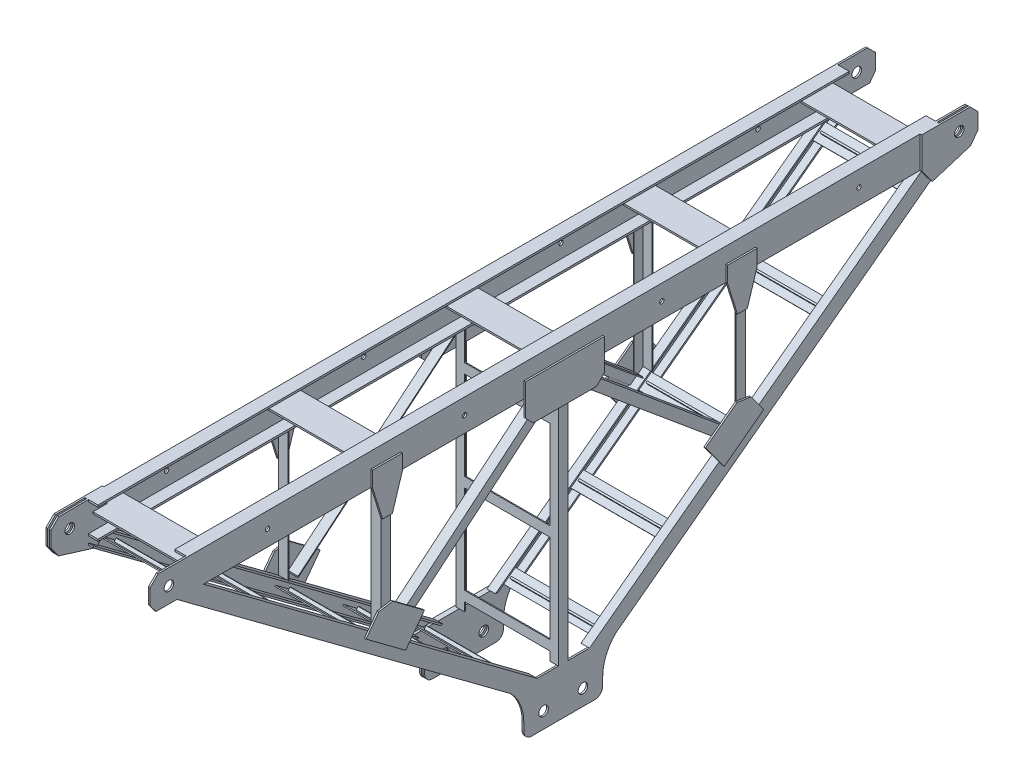
SolidWorks part; units mm, degrees
ref_plane "前视基准面" through (0, 0, 0) normal (0, 0, 1) x (1, 0, 0)
ref_plane "上视基准面" through (0, 0, 0) normal (0, 1, 0) x (1, 0, 0)
ref_plane "右视基准面" through (0, 0, 0) normal (1, 0, 0) x (0, 0, -1)
sketch "草图2" plane through (0, 0, 0) normal (0, 0, 1) x (1, 0, 0)
  line L0 (0, 0) -> (0, 160)
  line L1 (0, 160) -> (65, 160)
  line L2 (65, 160) -> (65, 150)
  line L3 (65, 150) -> (8.5, 150)
  line L4 (8.5, 150) -> (8.5, 10)
  line L5 (8.5, 10) -> (65, 10)
  line L6 (65, 10) -> (65, 0)
  line L7 (65, 0) -> (0, 0)
  line L8 (455, 160) -> (520, 160)
  line L9 (520, 160) -> (520, 0)
  line L10 (520, 0) -> (455, 0)
  line L11 (455, 0) -> (455, 10)
  line L12 (455, 10) -> (511.5, 10)
  line L13 (511.5, 10) -> (511.5, 150)
  line L14 (511.5, 150) -> (455, 150)
  line L15 (455, 150) -> (455, 160)
  dimension "D1" = 160
  dimension "D2" = 10
  dimension "D3" = 8.5
  dimension "D4" = 65
  dimension "D5" = 520
extrude "拉伸1" add sketch "草图2" along normal blind 4190
sketch "草图7" plane through (520, 0, 0) normal (1, 0, 0) x (0, 0, -1)
  line L1 (-2295, -1260) -> (-1895, -1260)
  line L2 (-2295, -1260) -> (-2295, -1500)
  line L3 (-2295, -1500) -> (-1895, -1500)
  line L4 (-1895, -1260) -> (-1895, -1500)
  line L5 (-4190, 160) -> (0, 160) construction
  line L6 (-2095, 160) -> (-2095, -1500) construction
  dimension "D1" = 240
  dimension "D2" = 400
  dimension "D4" = 1660
extrude "拉伸4" add sketch "草图7" against normal blind 520 separate body
sketch "草图8" plane through (0, -1260, 0) normal (0, 1, 0) x (1, 0, 0)
  line L0 (0, -2295) -> (520, -2295) construction
  line L1 (511.5, -2295) -> (8.5, -2295)
  line L2 (511.5, -2295) -> (511.5, -1895)
  line L3 (511.5, -1895) -> (8.5, -1895)
  line L4 (8.5, -2295) -> (8.5, -1895)
  line L5 (0, -1895) -> (520, -1895) construction
  line L6 (0, -1895) -> (0, -2295) construction
  line L7 (520, -1895) -> (520, -2295) construction
  dimension "D1" = 8.5
  dimension "D2" = 8.5
extrude "拉伸5" cut sketch "草图8" against normal through all
sketch "草图9" plane through (520, 0, 0) normal (1, 0, 0) x (0, 0, -1)
  line L0 (-2295, -1500) -> (-1895, -1500) construction
  circle A0 centre (-2195, -1420) radius 11
  circle A1 centre (-1995, -1420) radius 11
  point P6 (-2095, -1500)
  dimension "D1" = 22
  dimension "D2" = 80
  dimension "D3" = 80
  dimension "D4" = 200
  dimension "D5" = 100
extrude "拉伸6" cut sketch "草图9" against normal through all
sketch "草图13" plane through (520, 0, 0) normal (1, 0, 0) x (0, 0, -1)
  line L0 (-2295, -1260) -> (-4095, 80) construction
  line L1 (-95, 80) -> (-1895, -1260) construction
  line L2 (-1961.9855, -1260) -> (-1895, -1260)
  line L3 (-1895, -1260) -> (-2295, -1260) construction
  line L4 (-1895, -1260) -> (-1895, -1309.867)
  line L5 (-1895, -1500) -> (-1895, -1260) construction
  line L6 (-1895, -1309.867) -> (-135.4772, 0)
  line L7 (-4190, 0) -> (0, 0) construction
  line L8 (-135.4772, 0) -> (-269.4482, 0)
  line L9 (-269.4482, 0) -> (-1961.9855, -1260)
  line L10 (-2228.0145, -1260) -> (-2295, -1260)
  line L11 (-2295, -1260) -> (-2295, -1309.867)
  line L12 (-2295, -1260) -> (-2295, -1500) construction
  line L13 (-2295, -1309.867) -> (-4054.5228, 0)
  line L14 (-4054.5228, 0) -> (-3920.5518, 0)
  line L15 (-3920.5518, 0) -> (-2228.0145, -1260)
  line L16 (-4190, 160) -> (0, 160) construction
  line L17 (-4190, 0) -> (-4190, 160) construction
  line L18 (0, 0) -> (0, 160) construction
  dimension "D1" = 80
  dimension "D2" = 40
  dimension "D3" = 80
  dimension "D4" = 40
  dimension "D5" = 80
  dimension "D6" = 95
  dimension "D7" = 95
  dimension "D8" = 80
extrude "拉伸8" add sketch "草图13" against normal blind 43 separate body
sketch "草图14" plane through (477, 0, 0) normal (-1, 0, 0) x (0, 0, 1)
  line L0 (3933.9489, 0) -> (4041.1257, 0)
  line L1 (3920.5518, 0) -> (4054.5228, 0) construction
  line L2 (4041.1257, 0) -> (2295, -1299.8936)
  line L3 (2295, -1309.867) -> (2295, -1260) construction
  line L4 (2295, -1299.8936) -> (2295, -1260)
  line L5 (2295, -1260) -> (2241.4116, -1260)
  line L6 (2295, -1260) -> (2228.0145, -1260) construction
  line L7 (2241.4116, -1260) -> (3933.9489, 0)
  line L8 (4054.5228, 0) -> (2295, -1309.867) construction
  line L9 (2228.0145, -1260) -> (3920.5518, 0) construction
  line L10 (148.8743, 0) -> (256.0511, 0)
  line L11 (135.4772, 0) -> (269.4482, 0) construction
  line L12 (256.0511, 0) -> (1948.5884, -1260)
  line L13 (1961.9855, -1260) -> (1895, -1260) construction
  line L14 (1948.5884, -1260) -> (1895, -1260)
  line L15 (1895, -1260) -> (1895, -1299.8936)
  line L16 (1895, -1260) -> (1895, -1309.867) construction
  line L17 (1895, -1299.8936) -> (148.8743, 0)
  line L18 (1895, -1309.867) -> (135.4772, 0) construction
  line L19 (269.4482, 0) -> (1961.9855, -1260) construction
  dimension "D1" = 8
  dimension "D2" = 8
  dimension "D3" = 8
  dimension "D4" = 8
extrude "拉伸9" cut sketch "草图14" against normal blind 38
sketch "草图15" plane through (0, 0, 0) normal (-1, 0, 0) x (0, 0, 1)
  line L0 (4095, 80) -> (2295, -1260) construction
  line L1 (1895, -1500) -> (1895, -1260) construction
  line L2 (1895, -1260) -> (95, 80) construction
  line L3 (1895, -1260) -> (2295, -1260) construction
  line L4 (3920.5518, 0) -> (4054.5228, 0)
  line L5 (4190, 0) -> (0, 0) construction
  line L6 (4190, 0) -> (0, 0) construction
  line L7 (4054.5228, 0) -> (2295, -1309.867)
  line L8 (2295, -1260) -> (2295, -1500) construction
  line L9 (2295, -1309.867) -> (2295, -1260)
  line L10 (2295, -1260) -> (2228.0145, -1260)
  line L11 (2228.0145, -1260) -> (3920.5518, 0)
  line L12 (135.4772, 0) -> (269.4482, 0)
  line L13 (269.4482, 0) -> (1961.9855, -1260)
  line L14 (1961.9855, -1260) -> (1895, -1260)
  line L15 (1895, -1260) -> (1895, -1309.867)
  line L16 (1895, -1309.867) -> (135.4772, 0)
  line L17 (0, 0) -> (0, 160) construction
  line L18 (4190, 0) -> (4190, 160) construction
  line L19 (4190, 160) -> (0, 160) construction
  dimension "D1" = 40
  dimension "D2" = 40
  dimension "D3" = 80
  dimension "D4" = 40
  dimension "D5" = 80
  dimension "D6" = 95
  dimension "D7" = 95
  dimension "D8" = 80
extrude "拉伸10" add sketch "草图15" against normal blind 43 separate body
sketch "草图16" plane through (43, 0, 0) normal (1, 0, 0) x (0, 0, -1)
  line L0 (-3933.9489, 0) -> (-4041.1257, 0)
  line L1 (-4054.5228, 0) -> (-3920.5518, 0) construction
  line L2 (-4041.1257, 0) -> (-2295, -1299.8936)
  line L3 (-2295, -1260) -> (-2295, -1309.867) construction
  line L4 (-2295, -1299.8936) -> (-2295, -1260)
  line L5 (-2295, -1260) -> (-2241.4116, -1260)
  line L6 (-2228.0145, -1260) -> (-2295, -1260) construction
  line L7 (-2241.4116, -1260) -> (-3933.9489, 0)
  line L8 (-256.0511, 0) -> (-148.8743, 0)
  line L9 (-269.4482, 0) -> (-135.4772, 0) construction
  line L10 (-148.8743, 0) -> (-1895, -1299.8936)
  line L11 (-1895, -1309.867) -> (-1895, -1260) construction
  line L12 (-1895, -1299.8936) -> (-1895, -1260)
  line L13 (-1895, -1260) -> (-1948.5884, -1260)
  line L14 (-1895, -1260) -> (-1961.9855, -1260) construction
  line L15 (-1948.5884, -1260) -> (-256.0511, 0)
  line L16 (-135.4772, 0) -> (-1895, -1309.867) construction
  line L17 (-1961.9855, -1260) -> (-269.4482, 0) construction
  line L18 (-2295, -1309.867) -> (-4054.5228, 0) construction
  line L19 (-3920.5518, 0) -> (-2228.0145, -1260) construction
  dimension "D1" = 8
  dimension "D2" = 8
  dimension "D3" = 8
  dimension "D4" = 8
extrude "拉伸11" cut sketch "草图16" against normal blind 38
sketch "草图17" plane through (0, 0, 0) normal (-1, 0, 0) x (0, 0, 1)
  line L0 (4190, 160) -> (0, 160) construction
  line L1 (4190, 0) -> (0, 0) construction
  line L2 (2070, 0) -> (2120, 0)
  line L3 (2070, 0) -> (2070, -1260)
  line L4 (2070, -1260) -> (2120, -1260)
  line L5 (2120, 0) -> (2120, -1260)
  line L6 (1895, -1260) -> (2295, -1260) construction
  line L7 (2970, 0) -> (2970, -707.633)
  line L8 (3920.5518, 0) -> (2228.0145, -1260) construction
  line L9 (2970, -707.633) -> (3020, -670.4108)
  line L10 (3020, -670.4108) -> (3020, 0)
  line L11 (3020, 0) -> (2970, 0)
  line L12 (1170, 0) -> (1170, -670.4108)
  line L13 (4190, 160) -> (0, 160) construction
  line L14 (1170, -670.4108) -> (1220, -707.633)
  line L16 (1220, -707.633) -> (1220, 0)
  line L17 (1220, 0) -> (1170, 0)
  line L18 (1961.9855, -1260) -> (269.4482, 0) construction
  point P6 (2095, 160)
  point P22 (2095, 160)
  point P26 (2095, 160)
  dimension "D2" = 875
  dimension "D4" = 875
  dimension "D1" = 50
  dimension "D3" = 50
  dimension "D5" = 50
  dimension "D6" = 25
extrude "拉伸12" add sketch "草图17" against normal blind 520 separate body
sketch "草图18" plane through (0, -1260, 0) normal (0, -1, 0) x (1, 0, 0)
  line L0 (5, 2115) -> (43, 2115)
  line L1 (43, 2115) -> (43, 2120)
  line L2 (520, 2120) -> (0, 2120) construction
  line L3 (43, 2120) -> (477, 2120)
  line L4 (477, 2120) -> (477, 2115)
  line L5 (477, 2115) -> (515, 2115)
  line L6 (515, 2115) -> (515, 2070)
  line L9 (520, 2070) -> (0, 2070) construction
  line L10 (515, 2070) -> (5, 2070)
  line L14 (5, 2070) -> (5, 2115)
  line L15 (0, 2295) -> (0, 1895) construction
  line L16 (520, 2295) -> (520, 1895) construction
  dimension "D1" = 5
  dimension "D2" = 5
  dimension "D3" = 5
  dimension "D4" = 43
extrude "拉伸13" cut sketch "草图18" against normal blind 1260
sketch "草图22" plane through (0, 0, 3020) normal (0, 0, 1) x (1, 0, 0)
  line L0 (520, 0) -> (0, 0) construction
  line L1 (65, 0) -> (455, 0)
  line L2 (65, 0) -> (65, -1000)
  line L3 (65, -1000) -> (455, -1000)
  line L4 (455, 0) -> (455, -1000)
  line L6 (520, 0) -> (520, -1309.867) construction
  line L7 (0, -1309.867) -> (0, 0) construction
  dimension "D1" = 65
  dimension "D2" = 65
  dimension "D3" = 1000
extrude "拉伸14" cut sketch "草图22" against normal through all
sketch "草图23" plane through (455, 0, 0) normal (-1, 0, 0) x (0, 0, 1)
  line L1 (1170, 0) -> (1220, 0)
  line L2 (1170, 0) -> (1170, -707.633)
  line L3 (1170, -707.633) -> (1220, -707.633)
  line L4 (1220, 0) -> (1220, -707.633)
  line L5 (3020, 0) -> (2970, 0)
  line L6 (3020, 0) -> (3020, -707.633)
  line L7 (3020, -707.633) -> (2970, -707.633)
  line L8 (2970, 0) -> (2970, -707.633)
extrude "拉伸15" cut sketch "草图23" against normal blind 15
sketch "草图25" plane through (65, 0, 0) normal (1, 0, 0) x (0, 0, -1)
  line L1 (-2970, -707.633) -> (-3020, -707.633)
  line L2 (-2970, -707.633) -> (-2970, 0)
  line L3 (-2970, 0) -> (-3020, 0)
  line L4 (-3020, -707.633) -> (-3020, 0)
  line L5 (-1220, -707.633) -> (-1170, -707.633)
  line L6 (-1220, -707.633) -> (-1220, 0)
  line L7 (-1220, 0) -> (-1170, 0)
  line L8 (-1170, -707.633) -> (-1170, 0)
extrude "拉伸16" cut sketch "草图25" against normal blind 15
sketch "草图26" plane through (50, 0, 0) normal (1, 0, 0) x (0, 0, -1)
  line L0 (-3015, 0) -> (-2970, 0)
  line L1 (-2970, 0) -> (-3020, 0) construction
  line L2 (-2970, 0) -> (-2970, -707.633)
  line L3 (-2970, -707.633) -> (-3015, -674.133)
  line L4 (-2970, -707.633) -> (-3020, -670.4108) construction
  line L5 (-3015, -674.133) -> (-3015, 0)
  line L6 (-1175, 0) -> (-1220, 0)
  line L7 (-1170, 0) -> (-1220, 0) construction
  line L8 (-1220, 0) -> (-1220, -707.633)
  line L9 (-1220, -707.633) -> (-1175, -674.133)
  line L10 (-1220, -707.633) -> (-1170, -670.4108) construction
  line L11 (-1175, -674.133) -> (-1175, 0)
  line L12 (-1170, -670.4108) -> (-1170, 0) construction
  line L13 (-3020, 0) -> (-3020, -670.4108) construction
  dimension "D1" = 5
  dimension "D2" = 5
extrude "拉伸17" cut sketch "草图26" against normal blind 45
sketch "草图27" plane through (470, 0, 0) normal (-1, 0, 0) x (0, 0, 1)
  line L0 (3015, 0) -> (2970, 0)
  line L1 (3020, 0) -> (2970, 0) construction
  line L2 (2970, 0) -> (2970, -707.633)
  line L3 (2970, -707.633) -> (3015, -674.133)
  line L4 (2970, -707.633) -> (3020, -670.4108) construction
  line L5 (3015, -674.133) -> (3015, 0)
  line L6 (1175, 0) -> (1220, 0)
  line L7 (1220, 0) -> (1170, 0) construction
  line L8 (1220, 0) -> (1220, -707.633)
  line L9 (1220, -707.633) -> (1175, -674.133)
  line L10 (1220, -707.633) -> (1170, -670.4108) construction
  line L11 (1175, -674.133) -> (1175, 0)
  line L12 (3020, -670.4108) -> (3020, 0) construction
  line L13 (1170, 0) -> (1170, -670.4108) construction
  dimension "D1" = 5
  dimension "D2" = 5
extrude "拉伸18" cut sketch "草图27" against normal blind 45
sketch "草图28" plane through (0, 0, 0) normal (-1, 0, 0) x (0, 0, 1)
  line L0 (2070, 0) -> (1220, -707.633) construction
  line L1 (2970, -707.633) -> (2120, 0) construction
  line L2 (2120, -32.5295) -> (2120, 0)
  line L3 (2120, -1260) -> (2120, 0) construction
  line L4 (2120, 0) -> (2159.0741, 0)
  line L5 (4190, 0) -> (0, 0) construction
  line L6 (2159.0741, 0) -> (2970, -675.1035)
  line L7 (2970, 0) -> (2970, -707.633) construction
  line L8 (2970, -675.1035) -> (2970, -707.633)
  line L9 (2970, -707.633) -> (2949.3719, -722.9895)
  line L10 (3920.5518, 0) -> (2228.0145, -1260) construction
  line L11 (2949.3719, -722.9895) -> (2120, -32.5295)
  line L12 (2030.9259, 0) -> (2070, 0)
  line L13 (2070, 0) -> (2070, -32.5295)
  line L14 (2070, 0) -> (2070, -1260) construction
  line L15 (2070, -32.5295) -> (1240.6281, -722.9895)
  line L16 (1961.9855, -1260) -> (269.4482, 0) construction
  line L17 (1240.6281, -722.9895) -> (1220, -707.633)
  line L18 (1220, -707.633) -> (1220, -675.1035)
  line L19 (1220, -707.633) -> (1220, 0) construction
  line L20 (1220, -675.1035) -> (2030.9259, 0)
  dimension "D1" = 25
  dimension "D2" = 50
  dimension "D3" = 25
  dimension "D4" = 50
extrude "拉伸19" add sketch "草图28" against normal blind 50
sketch "草图29" plane through (50, 0, 0) normal (1, 0, 0) x (0, 0, -1)
  line L0 (-2038.7408, 0) -> (-2070, 0)
  line L1 (-2070, 0) -> (-2030.9259, 0) construction
  line L2 (-2070, 0) -> (-2070, -32.5295)
  line L3 (-2070, -32.5295) -> (-1240.6281, -722.9895)
  line L4 (-1240.6281, -722.9895) -> (-1220, -707.633)
  line L5 (-1220, -707.633) -> (-1220, -681.6094)
  line L6 (-1220, -675.1035) -> (-1220, -707.633) construction
  line L7 (-1220, -681.6094) -> (-2038.7408, 0)
  line L8 (-2030.9259, 0) -> (-1220, -675.1035) construction
  line L9 (-2151.2592, 0) -> (-2120, 0)
  line L10 (-2159.0741, 0) -> (-2120, 0) construction
  line L11 (-2120, 0) -> (-2120, -32.5295)
  line L12 (-2120, -32.5295) -> (-2949.3719, -722.9895)
  line L13 (-2949.3719, -722.9895) -> (-2970, -707.633)
  line L14 (-2970, -707.633) -> (-2970, -681.6094)
  line L15 (-2970, -707.633) -> (-2970, -675.1035) construction
  line L16 (-2970, -681.6094) -> (-2151.2592, 0)
  line L17 (-2970, -675.1035) -> (-2159.0741, 0) construction
  dimension "D1" = 5
  dimension "D2" = 5
extrude "拉伸20" cut sketch "草图29" against normal blind 45
sketch "草图30" plane through (520, 0, 0) normal (1, 0, 0) x (0, 0, -1)
  line L0 (-2070, 0) -> (-1220, -707.633) construction
  line L1 (-1240.6281, -722.9895) -> (-1175, -674.133) construction
  line L2 (-1220, -707.633) -> (-1220, 0) construction
  line L3 (-2120, 0) -> (-2970, -707.633) construction
  line L4 (-2070, 0) -> (-2030.9259, 0)
  line L5 (-4190, 0) -> (0, 0) construction
  line L6 (-2030.9259, 0) -> (-1220, -675.1035)
  line L7 (-1220, -675.1035) -> (-1220, -707.633)
  line L8 (-1220, -707.633) -> (-1240.6281, -722.9895)
  line L9 (-269.4482, 0) -> (-1961.9855, -1260) construction
  line L10 (-1240.6281, -722.9895) -> (-2070, -32.5295)
  line L11 (-2070, 0) -> (-2070, -1260) construction
  line L12 (-2070, -32.5295) -> (-2070, 0)
  line L13 (-2120, 0) -> (-2120, -32.5295)
  line L14 (-2120, -1260) -> (-2120, 0) construction
  line L15 (-2120, -32.5295) -> (-2949.3719, -722.9895)
  line L16 (-2228.0145, -1260) -> (-3920.5518, 0) construction
  line L17 (-2949.3719, -722.9895) -> (-2970, -707.633)
  line L18 (-2970, -707.633) -> (-2970, -675.1035)
  line L19 (-2970, 0) -> (-2970, -707.633) construction
  line L20 (-2970, -675.1035) -> (-2159.0741, 0)
  line L21 (-2159.0741, 0) -> (-2120, 0)
  dimension "D1" = 50
  dimension "D2" = 25
  dimension "D3" = 25
  dimension "D4" = 50
extrude "拉伸21" add sketch "草图30" against normal blind 50
sketch "草图31" plane through (470, 0, 0) normal (-1, 0, 0) x (0, 0, 1)
  line L0 (2120, 0) -> (2151.2592, 0)
  line L1 (2120, 0) -> (2159.0741, 0) construction
  line L2 (2151.2592, 0) -> (2970, -681.6094)
  line L3 (2970, -675.1035) -> (2970, -707.633) construction
  line L4 (2970, -681.6094) -> (2970, -707.633)
  line L5 (2970, -707.633) -> (2949.3719, -722.9895)
  line L6 (2949.3719, -722.9895) -> (2120, -32.5295)
  line L7 (2120, -32.5295) -> (2120, 0)
  line L8 (2038.7408, 0) -> (2070, 0)
  line L9 (2030.9259, 0) -> (2070, 0) construction
  line L10 (2070, 0) -> (2070, -32.5295)
  line L11 (2070, -32.5295) -> (1240.6281, -722.9895)
  line L12 (1240.6281, -722.9895) -> (1220, -707.633)
  line L13 (1220, -707.633) -> (1220, -681.6094)
  line L14 (1220, -707.633) -> (1220, -675.1035) construction
  line L15 (1220, -681.6094) -> (2038.7408, 0)
  line L16 (1220, -675.1035) -> (2030.9259, 0) construction
  line L17 (2159.0741, 0) -> (2970, -675.1035) construction
  dimension "D1" = 5
  dimension "D2" = 5
extrude "拉伸22" cut sketch "草图31" against normal blind 45
sketch "草图32" plane through (0, 0, 0) normal (-1, 0, 0) x (0, 0, 1)
  line L0 (0, 80) -> (4190, 80) construction
  line L1 (1120, 80) -> (1270, 80)
  line L2 (1895, 80) -> (2295, 80)
  line L3 (1895, 80) -> (1895, -120)
  line L4 (1895, -120) -> (2295, -120)
  line L5 (2295, 80) -> (2295, -120)
  line L6 (1270, 80) -> (1270, 0)
  line L7 (2030.9259, 0) -> (1220, 0) construction
  line L8 (1270, 0) -> (1220, -160)
  line L9 (1220, -675.1035) -> (1220, 0) construction
  line L10 (1220, -160) -> (1170, -160)
  line L11 (1170, 0) -> (1170, -670.4108) construction
  line L12 (1170, -160) -> (1120, 0)
  line L13 (1170, 0) -> (269.4482, 0) construction
  line L14 (1120, 0) -> (1120, 80)
  line L15 (2920, 80) -> (3070, 80)
  line L16 (3070, 80) -> (3070, 0)
  line L17 (3920.5518, 0) -> (3020, 0) construction
  line L18 (3070, 0) -> (3020, -160)
  line L19 (3020, -670.4108) -> (3020, 0) construction
  line L20 (3020, -160) -> (2970, -160)
  line L21 (2970, 0) -> (2970, -675.1035) construction
  line L22 (2970, -160) -> (2920, 0)
  line L23 (2970, 0) -> (2159.0741, 0) construction
  line L24 (2920, 0) -> (2920, 80)
  line L25 (2807.6858, -666.3992) -> (3008.2193, -517.1132)
  line L26 (2807.6858, -666.3992) -> (2903.2289, -794.7406)
  line L27 (3008.2193, -517.1132) -> (3103.7624, -645.4546)
  line L28 (2903.2289, -794.7406) -> (3103.7624, -645.4546)
  line L29 (2295, -1309.867) -> (4054.5228, 0) construction
  line L30 (2970, -675.1035) -> (3033.3528, -760.2043) construction
  line L31 (1181.7807, -517.1132) -> (1382.3142, -666.3992)
  line L32 (1181.7807, -517.1132) -> (1086.2376, -645.4546)
  line L33 (1382.3142, -666.3992) -> (1286.7711, -794.7406)
  line L34 (1086.2376, -645.4546) -> (1286.7711, -794.7406)
  line L35 (4190, 160) -> (0, 160) construction
  line L36 (0, 0) -> (0, 160) construction
  line L37 (4190, 0) -> (4190, 160) construction
  line L38 (135.4772, 0) -> (1895, -1309.867) construction
  line L39 (1220, -675.1035) -> (1156.6472, -760.2043) construction
  point P8 (2095, 160)
  dimension "D3" = 200
  dimension "D1" = 400
  dimension "D2" = 200
  dimension "D4" = 150
  dimension "D5" = 240
  dimension "D6" = 150
  dimension "D7" = 240
  dimension "D8" = 250
  dimension "D9" = 160
  dimension "D10" = 50
  dimension "D11" = 125
  dimension "D12" = 250
  dimension "D13" = 160
  dimension "D14" = 50
  dimension "D15" = 125
extrude "拉伸23" add sketch "草图32" along normal blind 8.5
pattern_linear "阵列(线性)7" count 2 spacing 528.5 along (1, 0, 0) of "拉伸23"
sketch "草图33" plane through (0, 0, 0) normal (-1, 0, 0) x (0, 0, 1)
  line L0 (217.5, 86.5) -> (293.25, 86.5)
  line L1 (217.5, 95) -> (377.5, 95)
  line L2 (217.5, 95) -> (217.5, 86.5)
  line L3 (301.75, 86.5) -> (377.5, 86.5)
  line L4 (377.5, 95) -> (377.5, 86.5)
  line L5 (95, 80) -> (4190, 80) construction
  line L6 (293.25, 86.5) -> (293.25, 46.5)
  line L7 (293.25, 46.5) -> (301.75, 46.5)
  line L8 (301.75, 86.5) -> (301.75, 46.5)
  line L9 (0, 160) -> (0, 0) construction
  line L11 (4190, 0) -> (4190, 160) construction
  dimension "D1" = 160
  dimension "D2" = 8.5
  dimension "D3" = 40
  dimension "D4" = 15
  dimension "D5" = 122.5
  dimension "D6" = 95
extrude "拉伸24" add sketch "草图33" against normal blind 520
pattern_linear "阵列(线性)8" count 5 spacing 900 along (0, 0, 1) of "拉伸24"
sketch "草图34" plane through (0, 0, 0) normal (-1, 0, 0) x (0, 0, 1)
  line L0 (3033.3528, -760.2043) -> (2970, -675.1035) construction
  line L1 (2295, -1309.867) -> (4054.5228, 0) construction
  line L2 (2975.8889, -749.9994) -> (2978.8746, -754.0101)
  line L3 (2975.8889, -749.9994) -> (3040.0596, -702.2279)
  line L4 (2978.8746, -754.0101) -> (3043.0453, -706.2385)
  line L5 (3040.0596, -702.2279) -> (3043.0453, -706.2385)
  dimension "D1" = 5
  dimension "D2" = 80
  dimension "D3" = 40
  dimension "D4" = 37.5
extrude "拉伸25" add sketch "草图34" against normal blind 512
sketch "草图35" plane through (0, -1907.9835, 1420.3877) normal (0, 0.8021, -0.5971) x (1, 0, 0)
  line L1 (40, -1973.2037) -> (480, -1973.2037)
  line L2 (40, -1973.2037) -> (40, -1981.7037)
  line L3 (40, -1981.7037) -> (480, -1981.7037)
  line L4 (480, -1973.2037) -> (480, -1981.7037)
  line L7 (0, -2056.5567) -> (0, -1954.1491) construction
  line L8 (520, -2056.5567) -> (520, -1954.1491) construction
  line L9 (512, -2019.2037) -> (5, -2019.2037) construction
  dimension "D1" = 40
  dimension "D2" = 40
  dimension "D3" = 8.5
  dimension "D4" = 37.5
extrude "拉伸26" add sketch "草图35" along normal blind 15
pattern_linear "阵列(线性)9" count 3 spacing 430 along (0, -0.5971, -0.8021) of "拉伸25", "拉伸26"
pattern_linear "阵列(线性)10" count 3 spacing 550 along (0, 0.5971, 0.8021) of "拉伸25", "拉伸26"
ref_plane "基准面2" through (0, 0, 2095) normal (0, 0, 1) x (1, 0, 0)
mirror "镜向13" about plane through (0, 0, 2095) normal (0, 0, 1) of "阵列(线性)10", "阵列(线性)9", "拉伸26", "拉伸25"
sketch "草图36" plane through (520, 0, 0) normal (1, 0, 0) x (0, 0, -1)
  line L0 (-2120, -1260) -> (-2120, -120) construction
  line L1 (-2120, -665) -> (-2070, -665)
  line L2 (-2120, -665) -> (-2120, -715)
  line L3 (-2120, -715) -> (-2070, -715)
  line L4 (-2070, -665) -> (-2070, -715)
  line L5 (-2070, -120) -> (-2070, -1260) construction
  point P8 (-2070, -690)
  dimension "D1" = 50
  dimension "D2" = 25
extrude "拉伸27" add sketch "草图36" against normal blind 520
sketch "草图37" plane through (0, -665, 0) normal (0, 1, 0) x (1, 0, 0)
  line L1 (5, -2115) -> (515, -2115)
  line L2 (5, -2115) -> (5, -2070)
  line L3 (5, -2070) -> (515, -2070)
  line L4 (515, -2115) -> (515, -2070)
extrude "拉伸28" cut sketch "草图37" against normal blind 45
pattern_linear "阵列(线性)11" count 2 spacing 500 along (0, 1, 0) of "拉伸27", "拉伸28"
pattern_linear "阵列(线性)13" count 2 spacing 500 along (0, -1, 0) of "拉伸27", "拉伸28"
sketch "草图38" plane through (0, 160, 0) normal (0, 1, 0) x (1, 0, 0)
  line L0 (520, -4190) -> (520, 0) construction
  line L1 (8.5, 0) -> (511.5, 0)
  line L2 (8.5, 0) -> (8.5, -190)
  line L3 (8.5, -190) -> (511.5, -190)
  line L4 (511.5, 0) -> (511.5, -190)
  line L5 (0, -4190) -> (0, 0) construction
  line L6 (65, 0) -> (0, 0) construction
  line L8 (8.5, -4000) -> (511.5, -4000)
  line L9 (8.5, -4000) -> (8.5, -4190)
  line L10 (8.5, -4190) -> (511.5, -4190)
  line L11 (511.5, -4000) -> (511.5, -4190)
  dimension "D1" = 8.5
  dimension "D2" = 8.5
  dimension "D3" = 190
  dimension "D4" = 8.5
  dimension "D5" = 190
extrude "拉伸29" cut sketch "草图38" against normal through all
sketch "草图39" plane through (520, 0, 0) normal (1, 0, 0) x (0, 0, -1)
  line L0 (-285, 160) -> (0, 160)
  line L1 (-4190, 160) -> (0, 160) construction
  line L2 (0, 160) -> (0, 0)
  line L3 (0, 0) -> (-231.683, -71.6199)
  line L4 (-1895, -1309.867) -> (-135.4772, 0) construction
  line L5 (-285, 160) -> (-285, 0)
  line L6 (-1120, 0) -> (-269.4482, 0) construction
  line L7 (-285, 0) -> (-231.683, -71.6199)
  line L8 (-269.4482, 0) -> (-1104.152, -621.3906) construction
  dimension "D1" = 285
extrude "拉伸30" add sketch "草图39" along normal blind 8.5
pattern_linear "阵列(线性)14" count 2 spacing 17 along (-1, 0, 0) of "拉伸30"
sketch "草图41" plane through (0, 160, 0) normal (0, 1, 0) x (1, 0, 0)
  line L0 (528.5, 0) -> (503, 0) construction
  line L1 (511.5, 0) -> (520, 0)
  line L2 (511.5, 0) -> (511.5, -190)
  line L3 (511.5, -190) -> (520, -190)
  line L4 (520, 0) -> (520, -190)
  line L5 (528.5, 0) -> (528.5, -285) construction
  line L6 (503, 0) -> (503, -190) construction
  dimension "D1" = 190
  dimension "D2" = 8.5
  dimension "D3" = 8.5
extrude "拉伸31" cut sketch "草图41" against normal through all
sketch "草图42" plane through (528.5, 0, 0) normal (1, 0, 0) x (0, 0, -1)
  line L0 (0, 160) -> (-285, 160) construction
  line L1 (0, 0) -> (0, 160) construction
  circle A0 centre (-95, 80) radius 24.25
  dimension "D1" = 48.5
  dimension "D2" = 80
  dimension "D3" = 95
extrude "拉伸32" cut sketch "草图42" against normal through all
sketch "草图43" plane through (0, 0, 0) normal (-1, 0, 0) x (0, 0, 1)
  line L1 (4190, 160) -> (0, 160) construction
  line L2 (3905, 160) -> (3905, 0)
  line L3 (3920.5518, 0) -> (3070, 0) construction
  line L4 (3905, 0) -> (3958.317, -71.6199)
  line L5 (2295, -1309.867) -> (4054.5228, 0) construction
  line L6 (3958.317, -71.6199) -> (4190, 0)
  line L7 (4190, 160) -> (4190, 0) construction
  line L8 (4190, 0) -> (4190, 160)
  line L9 (3905, 160) -> (4190, 160)
  line L10 (3920.5518, 0) -> (3085.848, -621.3906) construction
  dimension "D1" = 285
extrude "拉伸33" add sketch "草图43" along normal blind 8.5
pattern_linear "阵列(线性)15" count 2 spacing 17 along (1, 0, 0) of "拉伸33"
sketch "草图44" plane through (0, 160, 0) normal (0, 1, 0) x (1, 0, 0)
  line L0 (17, -4190) -> (-8.5, -4190) construction
  line L1 (8.5, -4190) -> (0, -4190)
  line L2 (8.5, -4190) -> (8.5, -4000)
  line L3 (8.5, -4000) -> (0, -4000)
  line L4 (0, -4190) -> (0, -4000)
  line L5 (-8.5, -4190) -> (-8.5, -3905) construction
  line L6 (17, -4190) -> (17, -4000) construction
  dimension "D1" = 190
  dimension "D2" = 8.5
  dimension "D3" = 8.5
extrude "拉伸34" cut sketch "草图44" against normal blind 160
sketch "草图45" plane through (-8.5, 0, 0) normal (-1, 0, 0) x (0, 0, 1)
  line L0 (4190, 160) -> (3905, 160) construction
  line L3 (4190, 0) -> (4190, 160) construction
  circle A0 centre (4095, 80) radius 24.25
  dimension "D1" = 48.5
  dimension "D2" = 80
  dimension "D3" = 95
extrude "拉伸35" cut sketch "草图45" against normal through all
chamfer "倒角1" distance 50 angle 45 4 edges at (-4.25, -517.1132, 1181.7807) (-4.25, -517.1132, 3008.2193) (524.25, -517.1132, 3008.2193) (524.25, -517.1132, 1181.7807)
sketch "草图47" plane through (0, 0, 0) normal (-1, 0, 0) x (0, 0, 1)
  line L0 (1828.0145, -1260) -> (2361.9855, -1260)
  line L1 (135.4772, 0) -> (1895, -1309.867) construction
  line L2 (2295, -1309.867) -> (3958.317, -71.6199) construction
  line L3 (1895, -1260) -> (2295, -1260) construction
  line L4 (1895, -1420) -> (1895, -1500)
  line L5 (1895, -1500) -> (1895, -1260) construction
  line L6 (1895, -1500) -> (2295, -1500)
  line L7 (2295, -1500) -> (2295, -1420)
  line L8 (2295, -1260) -> (2295, -1500) construction
  arc A0 (2295, -1420) -> (2361.9855, -1260) centre (2519.5789, -1420) cw
  arc A1 (1895, -1420) -> (1828.0145, -1260) centre (1670.4211, -1420) ccw
  dimension "D1" = 80
extrude "拉伸37" add sketch "草图47" along normal blind 8.5
pattern_linear "阵列(线性)16" count 3 spacing 8.5 along (1, 0, 0) of "拉伸37"
sketch "草图48" plane through (0, -1500, 0) normal (0, -1, 0) x (1, 0, 0)
  line L0 (17, 1895) -> (17, 2295) construction
  line L1 (8.5, 2395) -> (0, 2395)
  line L2 (8.5, 2395) -> (8.5, 1795)
  line L3 (8.5, 1795) -> (0, 1795)
  line L4 (0, 2395) -> (0, 1795)
  line L5 (-8.5, 1895) -> (-8.5, 2295) construction
  line L6 (-8.5, 2295) -> (17, 2295) construction
  line L7 (-8.5, 1895) -> (17, 1895) construction
  dimension "D1" = 8.5
  dimension "D2" = 8.5
  dimension "D3" = 100
  dimension "D4" = 100
extrude "拉伸38" cut sketch "草图48" against normal blind 160
sketch "草图49" plane through (520, 0, 0) normal (1, 0, 0) x (0, 0, -1)
  line L0 (-2361.9855, -1260) -> (-1828.0145, -1260)
  line L1 (-4054.5228, 0) -> (-2295, -1309.867) construction
  line L2 (-1895, -1309.867) -> (-231.683, -71.6199) construction
  line L3 (-1895, -1260) -> (-2295, -1260) construction
  line L4 (-2295, -1420) -> (-2295, -1500)
  line L5 (-2295, -1260) -> (-2295, -1500) construction
  line L6 (-2295, -1500) -> (-1895, -1500)
  line L7 (-1895, -1500) -> (-1895, -1420)
  line L8 (-1895, -1500) -> (-1895, -1260) construction
  arc A0 (-1895, -1420) -> (-1828.0145, -1260) centre (-1670.4211, -1420) cw
  arc A1 (-2295, -1420) -> (-2361.9855, -1260) centre (-2519.5789, -1420) ccw
  dimension "D1" = 80
extrude "拉伸39" add sketch "草图49" against normal blind 8.5
fillet "圆角2" radius 40 2 edges at (515.75, -1500, 2295) (515.75, -1500, 1895)
sketch "草图50" plane through (-8.5, 0, 0) normal (-1, 0, 0) x (0, 0, 1)
  line L0 (1935, -1500) -> (2255, -1500) construction
  circle A0 centre (1995, -1420) radius 24.25
  circle A1 centre (2195, -1420) radius 24.25
  point P8 (2095, -1500)
  dimension "D1" = 48.5
  dimension "D2" = 80
  dimension "D3" = 100
  dimension "D4" = 200
  dimension "D5" = 80
extrude "拉伸40" cut sketch "草图50" against normal through all
sketch "草图51" plane through (0, -1260, 0) normal (0, -1, 0) x (1, 0, 0)
  line L0 (511.5, 2120) -> (477, 2120) construction
  line L1 (17, 2620) -> (511.5, 2620)
  line L2 (17, 2620) -> (17, 1620)
  line L3 (17, 1620) -> (511.5, 1620)
  line L4 (511.5, 2620) -> (511.5, 1620)
  line L5 (511.5, 2120) -> (511.5, 2115) construction
  line L6 (17, 2120) -> (17, 2115) construction
  dimension "D1" = 1000
  dimension "D2" = 500
extrude "拉伸41" cut sketch "草图51" along normal through all
chamfer "倒角2" distance 40 angle 45 4 edges at (524.25, -120, 1895) (-4.25, -120, 1895) (-4.25, -120, 2295) (524.25, -120, 2295)
sketch "草图52" plane through (520, 0, 0) normal (1, 0, 0) x (0, 0, -1)
  line L0 (-4190, 160) -> (-285, 160) construction
  circle A0 centre (-3595, 80) radius 11
  circle A1 centre (-4095, 80) radius 24.25 construction
  dimension "D1" = 500
  dimension "D3" = 22
  dimension "D2" = 80
extrude "拉伸42" cut sketch "草图52" against normal through all
pattern_linear "阵列(线性)17" count 4 spacing 1000 along (0, 0, -1) of "拉伸42"
sketch "草图54" plane through (-8.5, 0, 0) normal (-1, 0, 0) x (0, 0, 1)
  line L0 (4190, 160) -> (4190, 120)
  line L1 (4190, 0) -> (4190, 160) construction
  line L2 (4190, 120) -> (4150, 160)
  line L3 (4190, 160) -> (3905, 160) construction
  line L4 (4150, 160) -> (4190, 160)
  line L5 (4190, 40) -> (4190, 0)
  line L6 (4190, 0) -> (4151.7843, -11.8136)
  line L7 (3958.317, -71.6199) -> (4190, 0) construction
  line L8 (4151.7843, -11.8136) -> (4190, 40)
  line L9 (0, 120) -> (40, 160)
  line L10 (0, 160) -> (0, 0) construction
  line L11 (3905, 160) -> (0, 160) construction
  line L12 (40, 160) -> (0, 160)
  line L13 (0, 160) -> (0, 120)
  line L14 (0, 40) -> (38.2157, -11.8136)
  line L16 (231.683, -71.6199) -> (0, 0) construction
  line L17 (0, 0) -> (0, 40)
  line L18 (38.2157, -11.8136) -> (0, 0)
  dimension "D1" = 40
extrude "拉伸43" cut sketch "草图54" against normal through all
